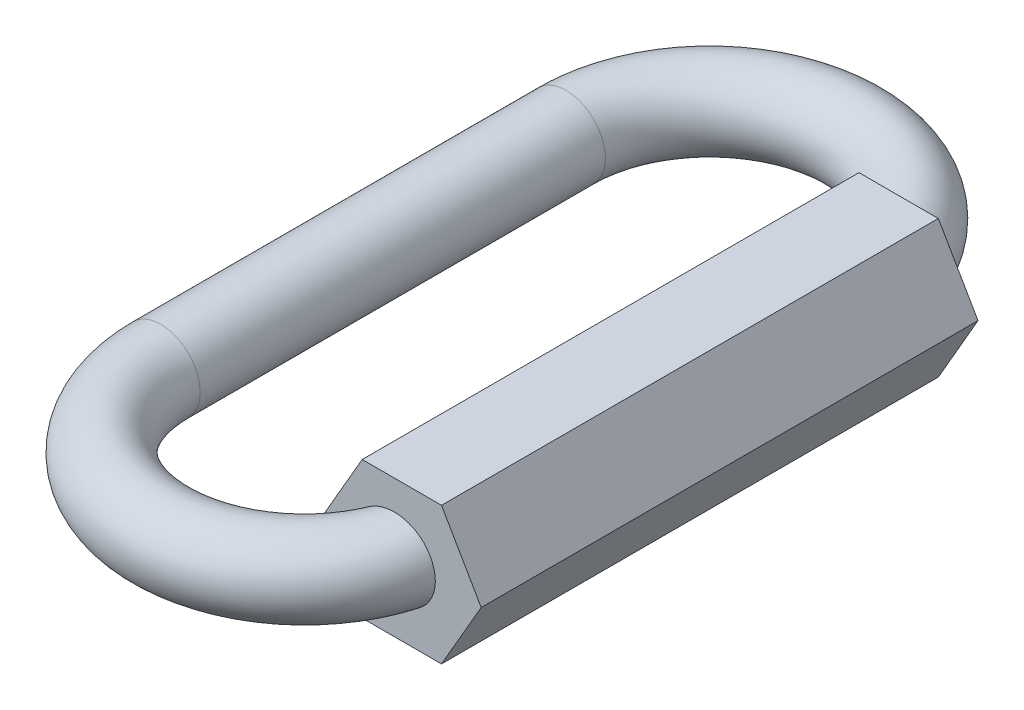
SolidWorks part; units mm, degrees
material "Plain Carbon Steel"
ref_plane "Front Plane" through (0, 0, 0) normal (0, 0, 1) x (1, 0, 0)
ref_plane "Top Plane" through (0, 0, 0) normal (0, 1, 0) x (1, 0, 0)
ref_plane "Right Plane" through (0, 0, 0) normal (1, 0, 0) x (0, 0, -1)
sketch "Sketch1" plane through (0, 0, 0) normal (0, 0, 1) x (1, 0, 0)
  circle A0 centre (0, 0) radius 2.53
  dimension "D1" = 5.06
sketch "Sketch2" plane through (0, 0, 0) normal (0, 1, 0) x (1, 0, 0)
  line L0 (0, -13.05) -> (0, 13.05)
  line L1 (-18.47, 13.05) -> (-18.47, -13.05)
  line L2 (0, 0) -> (-18.47, 0) construction
  arc A0 (0, 13.05) -> (-18.47, 13.05) centre (-9.235, 13.05) ccw
  arc A1 (0, -13.05) -> (-18.47, -13.05) centre (-9.235, -13.05) cw
  dimension "D1" = 44.57
  dimension "D2" = 18.47
sweep "Sweep1" add profiles "Sketch1" path "Sketch2"
sketch "Sketch3" plane through (0, 0, 0) normal (0, 0, 1) x (1, 0, 0)
  line L1 (-2.5548, 4.425) -> (-5.1095, 0)
  line L2 (-5.1095, 0) -> (-2.5548, -4.425)
  line L3 (-2.5548, -4.425) -> (2.5548, -4.425)
  line L4 (2.5548, -4.425) -> (5.1095, 0)
  line L5 (5.1095, 0) -> (2.5548, 4.425)
  line L6 (2.5548, 4.425) -> (-2.5548, 4.425)
  circle A0 centre (0, 0) radius 4.425 construction
  dimension "D1" = 8.85
extrude "Boss-Extrude1" add sketch "Sketch3" along normal blind 16 and the other way blind 16
sketch "Sketch4" plane through (0, 0, 0) normal (0, 1, 0) x (1, 0, 0)
  line L0 (-9.2432, -24.815) -> (-9.2432, -15.7962) construction
  circle A0 centre (-9.2432, -15.7962) radius 3.9688
  arc A1 (-21, -13.05) -> (2.1541, -16) centre (-9.235, -13.05) ccw construction
  point P7 (-9.2432, -19.765)
  dimension "D1" = 7.9375
  dimension "D2" = 5.05
